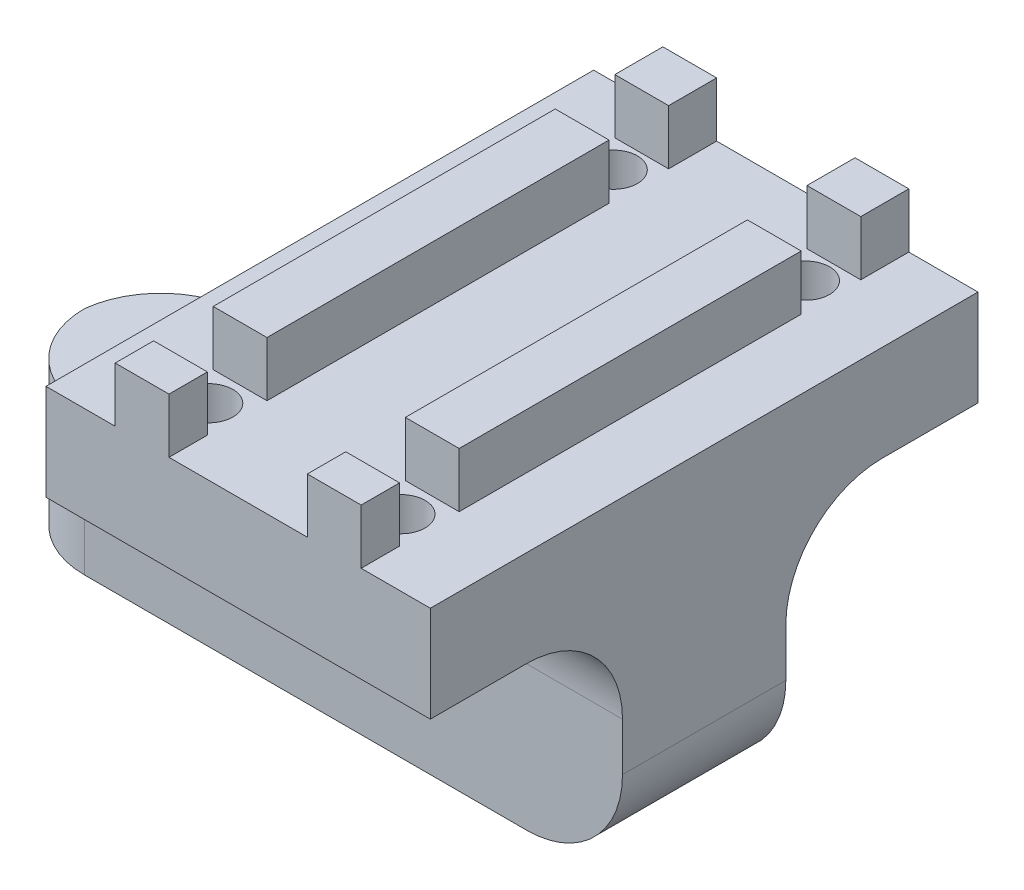
SolidWorks part; units mm, degrees
ref_plane "Alzado" through (0, 0, 0) normal (0, 0, 1) x (1, 0, 0)
ref_plane "Planta" through (0, 0, 0) normal (0, 1, 0) x (1, 0, 0)
ref_plane "Vista lateral" through (0, 0, 0) normal (1, 0, 0) x (0, 0, -1)
sketch "Croquis1" plane through (0, 0, 0) normal (0, 1, 0) x (1, 0, 0)
  line L1 (25, 20) -> (-65, 20)
  line L2 (25, 20) -> (25, -20)
  line L3 (-15, -20) -> (-65, -20)
  line L4 (-65, 20) -> (-65, -20)
  line L8 (25, -20) -> (25, -70)
  line L9 (25, -70) -> (-15, -70)
  line L10 (-15, -20) -> (-15, -70)
  point P0 (0, 0)
  dimension "D1" = 40
  dimension "D2" = 90
  dimension "D3" = 40
  dimension "D4" = 50
extrude "Saliente-Extruir1" add sketch "Croquis1" along normal blind 10
sketch "Croquis2" plane through (0, 0, 70) normal (0, 0, 1) x (1, 0, 0)
  line L27 (25, 10) -> (25, 0) construction
  line B0 (15, 15.7) -> (15, 1.4751) construction
  line B1 (12.2, 9.9874) -> (12.2, 15.7)
  line B2 (17.8, 15.7) -> (17.8, 9.9874)
  line B3 (15, 9.9874) -> (12.2, 9.9874)
  line B4 (12.2, 15.7) -> (17.8, 15.7)
  line B5 (17.8, 9.9874) -> (15, 9.9874)
  line B6 (-5, 15.7) -> (-5, 1.4751) construction
  line B7 (-7.8, 9.9874) -> (-7.8, 15.7)
  line B8 (-2.2, 15.7) -> (-2.2, 9.9874)
  line B9 (-5, 9.9874) -> (-7.8, 9.9874)
  line B10 (-7.8, 15.7) -> (-2.2, 15.7)
  line B11 (-2.2, 9.9874) -> (-5, 9.9874)
  dimension "D1" = 10
  dimension "D2" = 2
  dimension "D3" = 20
sketch_block_instance "Bloque1-1"
sketch_block "Bloque1" parameters "D1"=1.5, "D2"=4.6406
sketch_block_instance "Bloque1-2"
extrude "Saliente-Extruir2" add sketch "Croquis2" against normal through all
sketch "Croquis3" plane through (-65, 0, 0) normal (-1, 0, 0) x (0, 0, 1)
  line L13 (20, 10) -> (20, 0) construction
  line B0 (10, 15.7) -> (10, 10) construction
  line B1 (7.2, 10) -> (7.2, 15.7)
  line B2 (12.8, 15.7) -> (12.8, 10)
  line B3 (10, 10) -> (7.2, 10)
  line B4 (7.2, 15.7) -> (12.8, 15.7)
  line B5 (12.8, 10) -> (10, 10)
  line B6 (-12.8, 10) -> (-12.8, 15.7)
  line B7 (-7.2, 15.7) -> (-7.2, 10)
  line B8 (-10, 10) -> (-12.8, 10)
  line B9 (-12.8, 15.7) -> (-7.2, 15.7)
  line B10 (-7.2, 10) -> (-10, 10)
  dimension "D1" = 10
  dimension "D2" = 2
  dimension "D3" = 20
sketch_block_instance "Bloque2-1"
sketch_block "Bloque2" parameters "D1"=1.5, "D2"=6.3541
sketch_block_instance "Bloque2-2"
extrude "Saliente-Extruir3" add sketch "Croquis3" against normal blind 50
sketch "Croquis5" plane through (0, 15.7, 0) normal (0, 1, 0) x (1, 0, 0)
  line L0 (-15, -20) -> (-15, -70) construction
  line L1 (-15, -38) -> (25, -38)
  line L2 (-15, -38) -> (-15, -31.8)
  line L3 (-15, -31.8) -> (25, -31.8)
  line L4 (25, -38) -> (25, -31.8)
  line L5 (25, -70) -> (25, 20) construction
  line L6 (-15, -70) -> (-7.8, -70) construction
  line L7 (25, 20) -> (17.8, 20) construction
  line L12 (-65, 20) -> (-65, 12.8) construction
  line L13 (-65, -20) -> (-15, -20) construction
  line L14 (-55, -20) -> (-48.8, -20)
  line L15 (-55, -20) -> (-55, 0)
  line L16 (-55, 0) -> (-48.8, 0)
  line L17 (-48.8, -20) -> (-48.8, 0)
  line L19 (-65, 20) -> (-65, 12.8) construction
  line L20 (-25, 0) -> (-18.8, 0)
  line L21 (-25, 0) -> (-25, 20)
  line L22 (-25, 20) -> (-18.8, 20)
  line L23 (-18.8, 0) -> (-18.8, 20)
  line L24 (25, -70) -> (25, 20) construction
  line L25 (25, 10) -> (-15, 10)
  line L26 (25, 10) -> (25, 3.8)
  line L27 (25, 3.8) -> (-15, 3.8)
  line L28 (-15, 10) -> (-15, 3.8)
  line L30 (25, 20) -> (17.8, 20) construction
  dimension "D1" = 6.2
  dimension "D2" = 32
  dimension "D3" = 6.2
  dimension "D4" = 10
  dimension "D5" = 10
  dimension "D6" = 6.2
  dimension "D7" = 20
  dimension "D9" = 6.2
  dimension "D10" = 40
extrude "Cortar-Extruir1" cut sketch "Croquis5" against normal up to surface (5.7 mm away) up to face at (-35.4, 10, 10)
sketch "Croquis6" plane through (0, 10, 0) normal (0, 1, 0) x (1, 0, 0)
  line L0 (-19.1, 15) -> (-25, 5) construction
  line L1 (-25, 15) -> (-19.1, 5.7) construction
  line L2 (-55, -5) -> (-49.1, -15) construction
  line L3 (-49.1, -5) -> (-55, -15) construction
  line L4 (-2.8468, 5.7796) -> (-7.1532, 8.3204) construction
  line L5 (-15, -70) -> (-7.8, -70) construction
  line L6 (-2.8468, 8.3204) -> (-7.1532, 5.7796) construction
  line L7 (12.8468, 8.3204) -> (17.1532, 5.7796) construction
  line L8 (12.2, 20) -> (-2.2, 20) construction
  line L9 (-48.8, -12.8) -> (-48.8, -7.2) construction
  line L10 (-55, -7.2) -> (-65, -7.2) construction
  line L12 (17.1532, 8.3204) -> (12.8468, 5.7796) construction
  circle A0 centre (-52.05, -10) radius 2.5
  circle A1 centre (-22.05, 10) radius 2.5
  circle A4 centre (15, -35.05) radius 2.5
  circle A5 centre (-5, -35.05) radius 2.5
  circle A6 centre (-5, 7.05) radius 2.5
  circle A7 centre (15, 7.05) radius 2.5
  dimension "D1" = 5
  dimension "D4" = 3.25
  dimension "D2" = 34.95
  dimension "D3" = 12.95
  dimension "D5" = 2.8
extrude "Cortar-Extruir2" cut sketch "Croquis6" against normal up to next
sketch "Croquis10" plane through (-65, 0, 0) normal (-1, 0, 0) x (0, 0, 1)
  line L1 (-32.5361, -7.8321) -> (32.5361, -7.8321)
  line L2 (-32.5361, -7.8321) -> (-32.5361, 16.3469)
  line L3 (-32.5361, 16.3469) -> (32.5361, 16.3469)
  line L4 (32.5361, -7.8321) -> (32.5361, 16.3469)
  line L5 (-32.5361, -7.8321) -> (32.5361, 16.3469) construction
  line L6 (-32.5361, 16.3469) -> (32.5361, -7.8321) construction
  point P0 (0, 4.2574)
extrude "Cortar-Extruir6" cut sketch "Croquis10" against normal up to surface (50 mm away) up to face at (-15, 5, 45)
sketch "Croquis11" plane through (0, 0, 0) normal (0, -1, 0) x (1, 0, 0)
  line L0 (25, 70) -> (25, -20) construction
  line L1 (25, 5) -> (-45, 5)
  line L2 (25, 5) -> (25, 22)
  line L3 (25, 22) -> (-45, 22)
  line L4 (-45, 5) -> (-45, 22)
  line L6 (-15, 70) -> (25, 70) construction
  line L7 (-15, -20) -> (-15, 70) construction
  dimension "D1" = 65
  dimension "D2" = 30
  dimension "D3" = 17
extrude "Saliente-Extruir4" add sketch "Croquis11" along normal blind 25
sketch "Croquis12" plane through (0, 0, 0) normal (0, 1, 0) x (1, 0, 0)
  line L0 (-45, -22) -> (-45, -5) construction
  line L1 (-15, -22) -> (-45, -22) construction
  circle A0 centre (-30, -13.5) radius 4.5
  dimension "D3" = 9
  dimension "D1" = 15
  dimension "D2" = 8.5
extrude "Cortar-Extruir7" cut sketch "Croquis12" against normal through all
sketch "Croquis16" plane through (0, 0, 70) normal (0, 0, 1) x (1, 0, 0)
  line L1 (-23.3288, 32.3308) -> (31.801, 32.3308)
  line L2 (-23.3288, 32.3308) -> (-23.3288, -21.9807)
  line L3 (-23.3288, -21.9807) -> (31.801, -21.9807)
  line L4 (31.801, 32.3308) -> (31.801, -21.9807)
  line L5 (-23.3288, 32.3308) -> (31.801, -21.9807) construction
  line L6 (-23.3288, -21.9807) -> (31.801, 32.3308) construction
  point P0 (4.2361, 5.1751)
extrude "Cortar-Extruir11" cut sketch "Croquis16" against normal blind 23
fillet "Redondeo1" radius 10 1 edges at (5, 0, 22)
fillet "Redondeo2" radius 10 1 edges at (25, -25, 13.5)
fillet "Redondeo3" radius 10 1 edges at (5, 0, 5)
sketch "Croquis17" plane through (0, 0, -20) normal (0, 0, -1) x (-1, 0, 0)
  line L1 (25.5484, -12.7445) -> (-30.5685, -12.7445)
  line L2 (25.5484, -12.7445) -> (25.5484, 20.9858)
  line L3 (25.5484, 20.9858) -> (-30.5685, 20.9858)
  line L4 (-30.5685, -12.7445) -> (-30.5685, 20.9858)
  line L5 (25.5484, -12.7445) -> (-30.5685, 20.9858) construction
  line L6 (25.5484, 20.9858) -> (-30.5685, -12.7445) construction
  point P0 (-2.5101, 4.1206)
extrude "Cortar-Extruir12" cut sketch "Croquis17" against normal blind 5
sketch "Croquis18" plane through (0, 0, 47) normal (0, 0, 1) x (1, 0, 0)
  line L1 (-25.1428, 23.3399) -> (27.0992, 23.3399)
  line L2 (-25.1428, 23.3399) -> (-25.1428, -14.5717)
  line L3 (-25.1428, -14.5717) -> (27.0992, -14.5717)
  line L4 (27.0992, 23.3399) -> (27.0992, -14.5717)
  line L5 (-25.1428, 23.3399) -> (27.0992, -14.5717) construction
  line L6 (-25.1428, -14.5717) -> (27.0992, 23.3399) construction
  point P0 (0.9782, 4.3841)
extrude "Cortar-Extruir13" cut sketch "Croquis18" against normal blind 5
sketch "Croquis19" plane through (0, 0, 0) normal (0, 1, 0) x (1, 0, 0)
  line L0 (-15, -5) -> (-15, -22) construction
  line L1 (-15, 8.5168) -> (-45, 8.5168)
  line L2 (-15, 8.5168) -> (-15, -35.5168)
  line L3 (-15, -35.5168) -> (-45, -35.5168)
  line L4 (-45, 8.5168) -> (-45, -35.5168)
  line L5 (-15, 8.5168) -> (-45, -35.5168) construction
  line L6 (-15, -35.5168) -> (-45, 8.5168) construction
  point P0 (-30, -13.5)
extrude "Cortar-Extruir14" cut sketch "Croquis19" against normal blind 10
fillet "Redondeo4" radius 10 1 edges at (-15, -10, 13.5)
sketch "Croquis20" plane through (-45, 0, 0) normal (-1, 0, 0) x (0, 0, 1)
  line L1 (0.6603, -32.5764) -> (24.8869, -32.5764)
  line L2 (0.6603, -32.5764) -> (0.6603, -3.1841)
  line L3 (0.6603, -3.1841) -> (24.8869, -3.1841)
  line L4 (24.8869, -32.5764) -> (24.8869, -3.1841)
  line L5 (0.6603, -32.5764) -> (24.8869, -3.1841) construction
  line L6 (0.6603, -3.1841) -> (24.8869, -32.5764) construction
  point P0 (12.7736, -17.8802)
extrude "Cortar-Extruir15" cut sketch "Croquis20" against normal blind 5
fillet "Redondeo6" radius 9 1 edges at (-40, -17.5, 22)
fillet "Redondeo7" radius 9 1 edges at (-40, -17.5, 5)
sketch "Croquis21" plane through (0, 0, 5) normal (0, 0, -1) x (-1, 0, 0)
  line L0 (31.0557, -25) -> (31.0557, -10) construction
  circle A0 centre (31.0557, -17.5) radius 1.35
  dimension "D1" = 2.7
extrude "Cortar-Extruir16" cut sketch "Croquis21" against normal through all
